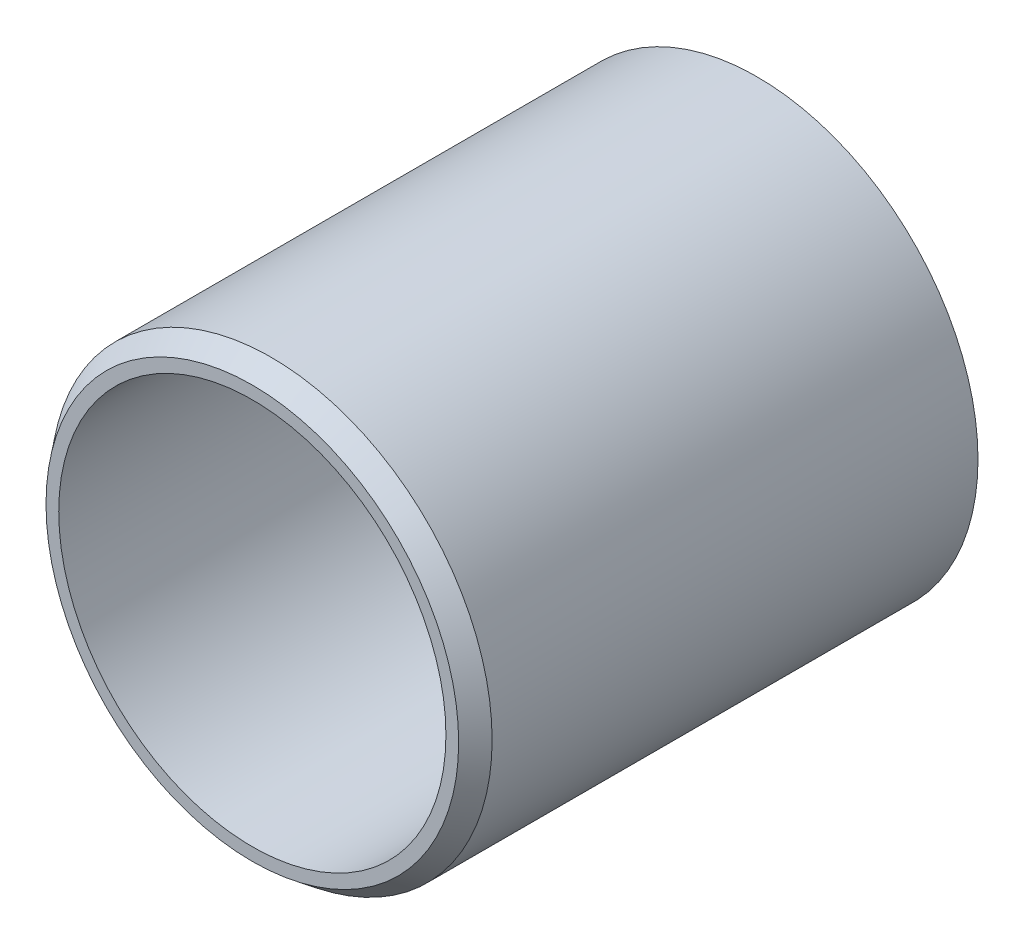
SolidWorks part; units mm, degrees
material "Plain Carbon Steel"
ref_plane "Front Plane" through (0, 0, 0) normal (0, 0, 1) x (1, 0, 0)
ref_plane "Top Plane" through (0, 0, 0) normal (0, 1, 0) x (1, 0, 0)
ref_plane "Right Plane" through (0, 0, 0) normal (1, 0, 0) x (0, 0, -1)
sketch "Sketch1" plane through (0, 0, 0) normal (0, 0, 1) x (1, 0, 0)
  circle A0 centre (0, 0) radius 44.45
  circle A1 centre (0, 0) radius 38.9636
  dimension "D1" = 88.9
  dimension "D2" = 5.4864
extrude "Extrude1" add sketch "Sketch1" along normal mid plane 101.6
ref_plane "Plane-Origin" through (0, 0, 0) normal (0, 0, 1) x (1, 0, 0)
ref_axis "Axis1" through (0, 0, 50.8) along (0, 0, -1)
chamfer "Chamfer3" [suppressed] distance 3.81 angle 37.5
chamfer "Chamfer4" distance 3.81 angle 37.5 1 edges at (44.45, 0, 50.8) first distance on face at (44.45, 0, 50.8)
